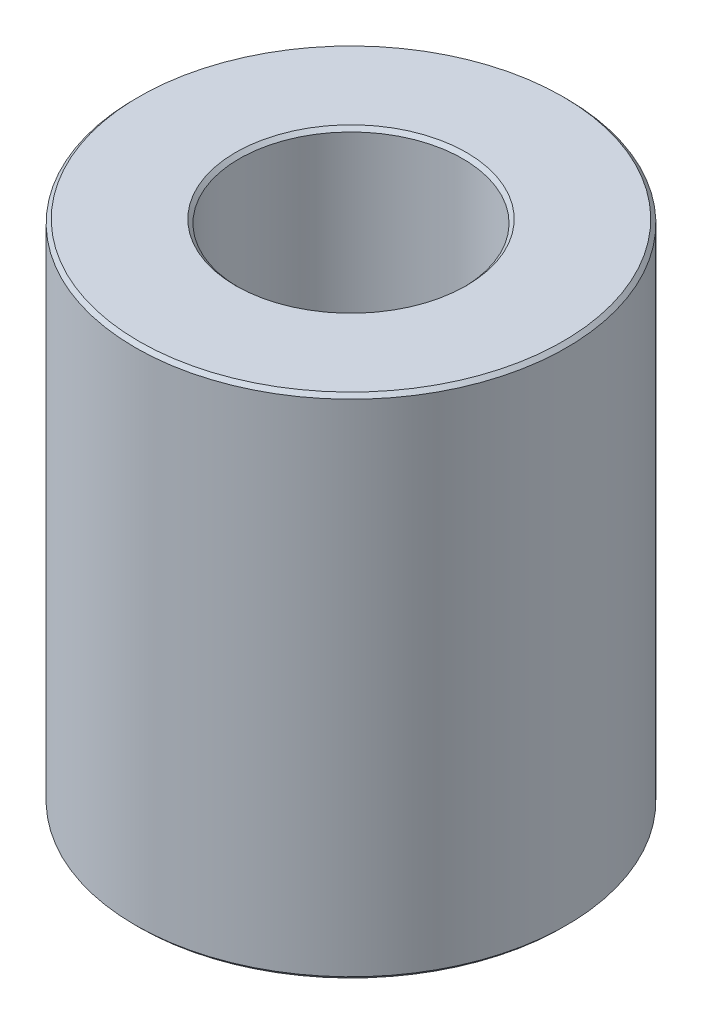
SolidWorks part; units mm, degrees
ref_plane "Front Plane" through (0, 0, 0) normal (0, 0, 1) x (1, 0, 0)
ref_plane "Top Plane" through (0, 0, 0) normal (0, 1, 0) x (1, 0, 0)
ref_plane "Right Plane" through (0, 0, 0) normal (1, 0, 0) x (0, 0, -1)
sketch "Sketch1" plane through (0, 0, 0) normal (0, 1, 0) x (1, 0, 0)
  circle A0 centre (0, 0) radius 42.5
  dimension "SLEEVE_OD" = 85
extrude "Boss-Extrude1" add sketch "Sketch1" along normal blind 100.0328
sketch "Sketch2" plane through (0, 0, 0) normal (0, 1, 0) x (1, 0, 0)
  circle A0 centre (0, 0) radius 22.0378
  dimension "BORE_D" = 44.0757
extrude "Cut-Extrude1" cut sketch "Sketch2" along normal through all
chamfer "Chamfer1" distance 0.7166 angle 45 4 edges at (0, 100.0328, 22.0378) (0, 0, 22.0378) (0, 0, 42.5) (0, 100.0328, 42.5)
